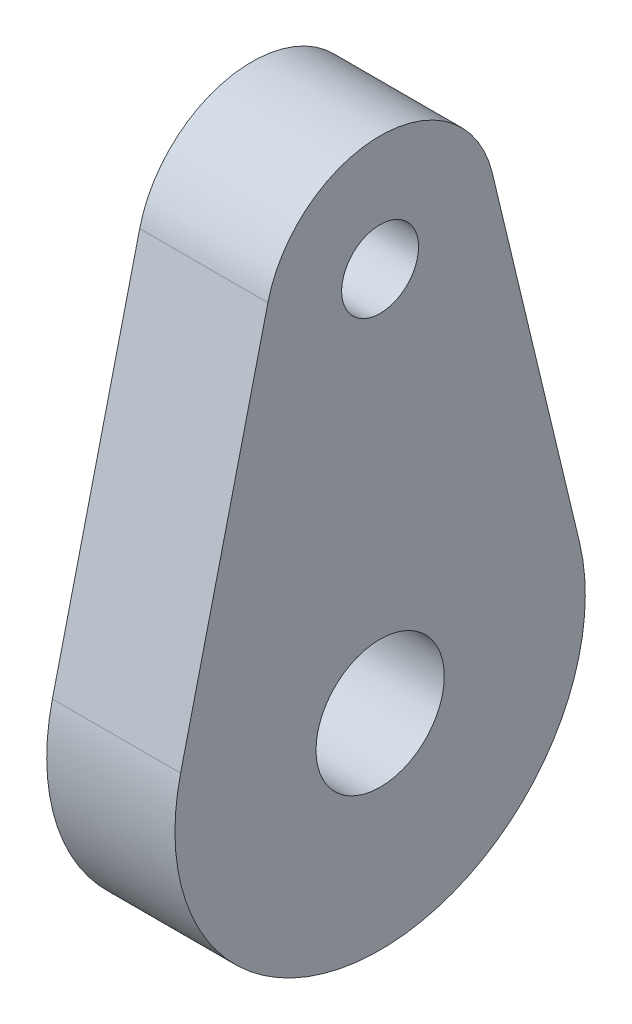
SolidWorks part; units mm, degrees
ref_plane "前视基准面" through (0, 0, 0) normal (0, 0, 1) x (1, 0, 0)
ref_plane "上视基准面" through (0, 0, 0) normal (0, 1, 0) x (1, 0, 0)
ref_plane "右视基准面" through (0, 0, 0) normal (1, 0, 0) x (0, 0, -1)
sketch "草图1" plane through (0, 0, 0) normal (1, 0, 0) x (0, 0, -1)
  line L0 (-7.7792, 1.8667) -> (-4.3758, 16.05)
  line L1 (0, 15) -> (0, 0) construction
  line L2 (4.3758, 16.05) -> (7.7792, 1.8667)
  arc A0 (4.3758, 16.05) -> (-4.3758, 16.05) centre (0, 15) ccw
  circle A1 centre (0, 0) radius 2.5
  arc A2 (-7.7792, 1.8667) -> (7.7792, 1.8667) centre (0, 0) ccw
  circle A3 centre (0, 15) radius 1.5
  dimension "D1" = 3
  dimension "D2" = 5
  dimension "D3" = 9
  dimension "D5" = 16
  dimension "D4" = 15
extrude "凸台-拉伸1" add sketch "草图1" along normal blind 5
sketch "草图2" plane through (0, 0, 0) normal (-1, 0, 0) x (0, 0, 1)
  circle A0 centre (0, 0) radius 4.5
  circle A1 centre (0, 0) radius 2.5 construction
  circle A2 centre (0, 0) radius 2.5
  dimension "D1" = 9
extrude "凸台-拉伸2" add sketch "草图2" along normal blind 1
